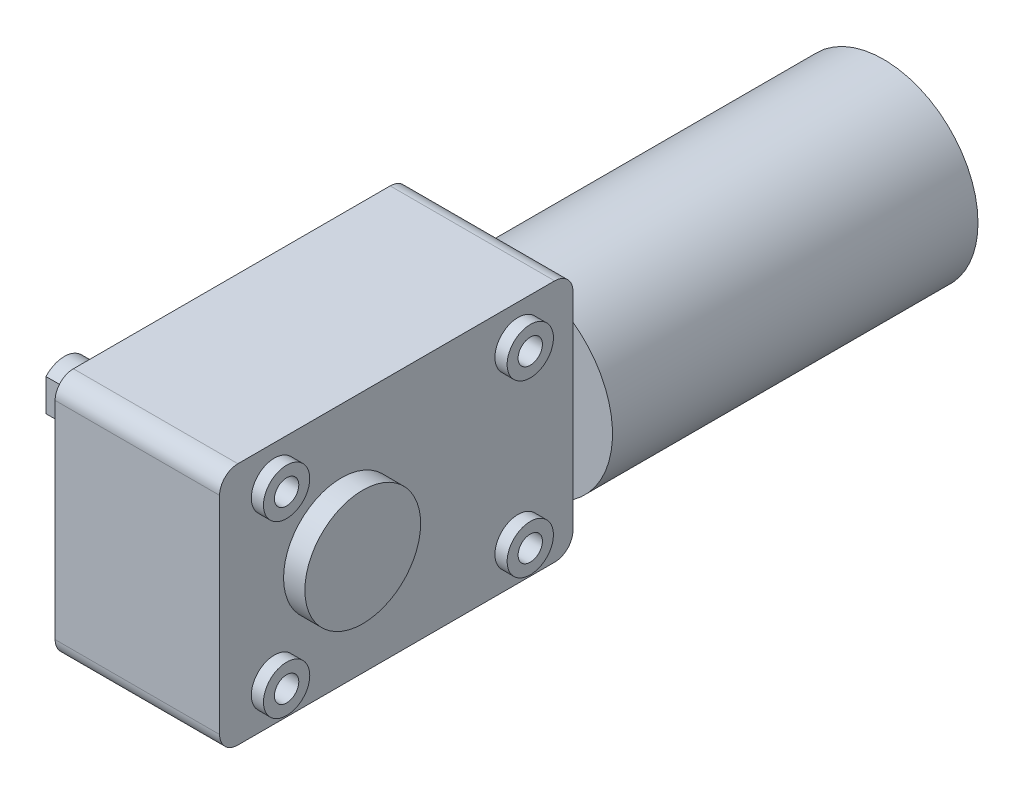
SolidWorks part; units mm, degrees
note: '?' marks a value the reader was unsure of.
ref_plane "Front Plane" through (0, 0, 0) normal (0, 0, 1) x (1, 0, 0)
ref_plane "Top Plane" through (0, 0, 0) normal (0, 1, 0) x (1, 0, 0)
ref_plane "Right Plane" through (0, 0, 0) normal (1, 0, 0) x (0, 0, -1)
sketch "Sketch1" plane through (0, 0, 0) normal (0, 0, 1) x (1, 0, 0)
  circle A0 centre (0, 0) radius 15.5
  dimension "D1" = 31
extrude "Boss-Extrude1" add sketch "Sketch1" along normal blind 60
sketch "Sketch2" plane through (0, 0, 0) normal (0, 0, -1) x (-1, 0, 0)
  circle A2 centre (0, 0) radius 6
  circle A3 centre (0, 0) radius 6
  dimension "D1" = 9.5
extrude "Boss-Extrude2" add sketch "Sketch2" along normal blind 2
sketch "Sketch3" plane through (0, 0, 0) normal (0, 1, 0) x (1, 0, 0)
  line L0 (0, 0) -> (0, -117.3957) construction
  line L1 (-15.5, -60) -> (15.5, -60) construction
  line L2 (9, -60) -> (-18, -60)
  line L3 (9, -60) -> (9, -118)
  line L4 (9, -118) -> (-18, -118)
  line L5 (-18, -60) -> (-18, -118)
  dimension "D1" = 27
  dimension "D2" = 58
  dimension "D3" = 18
extrude "Boss-Extrude3" add sketch "Sketch3" along normal mid plane 40
sketch "Sketch4" plane through (-18, 0, 0) normal (-1, 0, 0) x (0, 0, 1)
  line L0 (118, 20) -> (118, -20) construction
  circle A0 centre (98, 0) radius 9.5
  point P5 (118, 0)
  dimension "D1" = 19
  dimension "D2" = 20
extrude "Boss-Extrude4" add sketch "Sketch4" along normal blind 3.5
sketch "Sketch6" plane through (9, 0, 0) normal (1, 0, 0) x (0, 0, -1)
  line L0 (-118, 20) -> (-118, -20) construction
  circle A0 centre (-98, 0) radius 9.5
  dimension "D1" = 19
  dimension "D2" = 20
extrude "Boss-Extrude5" add sketch "Sketch6" along normal blind 3.5
sketch "Sketch7" plane through (-21.5, 0, 0) normal (-1, 0, 0) x (0, 0, 1)
  circle A1 centre (98, 0) radius 4
  circle A2 centre (98, 0) radius 9.5 construction
  dimension "D1" = 8
extrude "Boss-Extrude6" add sketch "Sketch7" along normal blind 15 contours A1
sketch "Sketch8" plane through (-36.5, 0, 0) normal (-1, 0, 0) x (0, 0, 1)
  line L6 (101, 2.6458) -> (101, -2.6458)
  arc A0 (101, -2.6458) -> (101, 2.6458) centre (98, 0) ccw
  circle A1 centre (98, 0) radius 4 construction
  point P8 (101, 0)
  dimension "D1" = 8
  dimension "D4" = 3
extrude "Cut-Extrude1" cut sketch "Sketch8" against normal blind 14
sketch "Sketch10" plane through (9, 0, 0) normal (1, 0, 0) x (0, 0, -1)
  line L0 (-89, 20) -> (-89, -20) construction
  line L1 (-118, 20) -> (-60, 20) construction
  line L2 (-118, -20) -> (-60, -20) construction
  line L3 (-118, 0) -> (-60, 0) construction
  line L4 (-118, 20) -> (-118, -20) construction
  line L5 (-60, 12.6194) -> (-60, -12.6194) construction
  circle A0 centre (-69, 14) radius 3.8
  circle A1 centre (-109, 14) radius 3.8
  circle A2 centre (-69, -14) radius 3.8
  circle A3 centre (-109, -14) radius 3.8
  dimension "D1" = 7.6
  dimension "D2" = 40
  dimension "D3" = 28
extrude "Boss-Extrude7" add sketch "Sketch10" along normal blind 2 and the other way offset from surface (29 mm away) 2 other way up to face at (-18, 0, 88.5)
hole_wizard "Ø4.0mm Dowel Hole1" positions "Sketch13" profile "Sketch14" hole size "Ø4.0" standard "ANSI Metric" end condition through all
sketch "Sketch13" plane through (11, 0, 0) normal (1, 0, 0) x (0, 0, -1)
  circle A0 centre (-109, 14) radius 3.8 construction
  circle A1 centre (-69, 14) radius 3.8 construction
  circle A2 centre (-69, -14) radius 3.8 construction
  circle A3 centre (-109, -14) radius 3.8 construction
  point P0 (-109, 14)
  point P2 (-69, 14)
  point P4 (-69, -14)
  point P6 (-109, -14)
sketch "Sketch14" plane through (11, 14, 109) normal (0, 1, 0) x (0, 0, -1)
  line L0 (0, 0) -> (0, 47.5)
  line L1 (0, 47.5) -> (2, 47.5)
  line L2 (2, 47.5) -> (2, 0)
  line L5 (2, 0) -> (0, 0)
  line L11 (0, -6.35) -> (0, 107.95) construction
  dimension "Thru Hole Dia." = 4
  dimension "Thru Hole Depth" = 47.5
fillet "Fillet1" radius 3 4 edges at (-4.5, -20, 60) (-4.5, -20, 118) (-4.5, 20, 118) (-4.5, 20, 60)
ref_point "Center Point 1"
ref_point "Center Point 2"
ref_axis "Shaft-axis" through (25.912, 0, 98) along (-1, 0, 0)?
